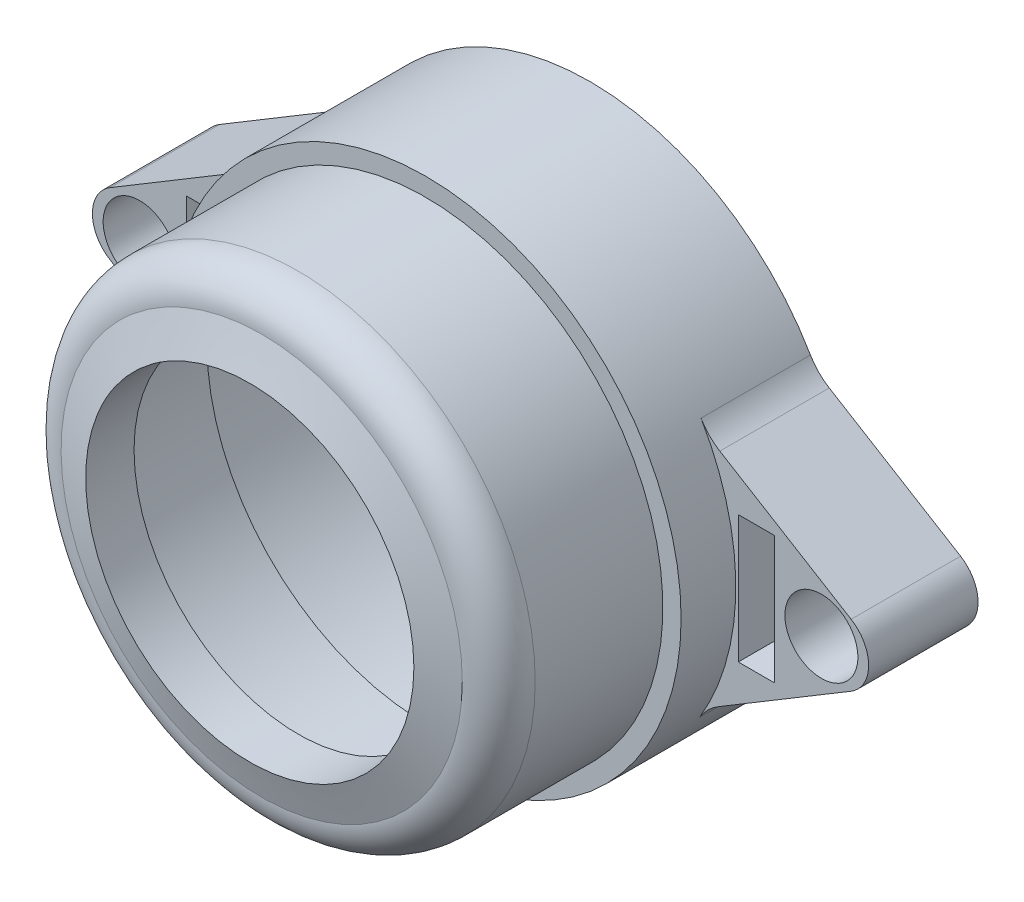
SolidWorks part; units mm, degrees
material "PE High Density"
ref_plane "Front" through (0, 0, 0) normal (0, 0, 1) x (1, 0, 0)
ref_plane "Top" through (0, 0, 0) normal (0, 1, 0) x (1, 0, 0)
ref_plane "Right" through (0, 0, 0) normal (1, 0, 0) x (0, 0, -1)
sketch "Sketch1" plane through (0, 0, 0) normal (0, 0, 1) x (1, 0, 0)
  circle A0 centre (0, 0) radius 14
extrude "Boss-Extrude1" add sketch "Sketch1" along normal blind 9 contours A0
sketch "Sketch2" plane through (0, 0, 9) normal (0, 0, 1) x (1, 0, 0)
  circle A0 centre (0, 0) radius 13
extrude "Boss-Extrude2" add sketch "Sketch2" along normal blind 9
fillet "Fillet1" radius 2 1 edges at (13, 0, 18)
sketch "Sketch3" plane through (0, 0, 18) normal (0, 0, 1) x (1, 0, 0)
  circle A0 centre (0, 0) radius 9
  circle A1 centre (0, 0) radius 8
extrude "Boss-Extrude4" add sketch "Sketch3" along normal blind 1 contours A1
loft "Loft2" add section edge at (8, 0, 19) section edge at (11, 0, 18) connector at (5.2489, -6.0373, 19) connector at (8.7002, -6.731, 18)
sketch "Sketch5" plane through (0, 0, 0) normal (0, 0, 1) x (1, 0, 0)
  line L0 (0, 14) -> (-23.147, 0.0997)
  line L1 (-23.147, 0.0997) -> (0, -14)
  line L2 (0, 14) -> (0, -14)
  circle A0 centre (0, 0) radius 14 construction
extrude "Boss-Extrude5" add sketch "Sketch5" along normal blind 6
sketch "Sketch6" plane through (0, 0, 6) normal (0, 0, 1) x (1, 0, 0)
  circle A0 centre (-18.6917, 0) radius 2
extrude "Cut-Extrude1" cut sketch "Sketch6" against normal blind 6
fillet "Fillet2" radius 2 1 edges at (-23.147, 0.0997, 3)
sketch "Sketch7" plane through (0, 0, 6) normal (0, 0, 1) x (1, 0, 0)
  line L1 (-16.134, 3.5) -> (-14.134, 3.5)
  line L2 (-16.134, 3.5) -> (-16.134, -3.5)
  line L3 (-16.134, -3.5) -> (-14.134, -3.5)
  line L4 (-14.134, 3.5) -> (-14.134, -3.5)
  line L5 (-16.134, 3.5) -> (-14.134, -3.5) construction
  line L6 (-16.134, -3.5) -> (-14.134, 3.5) construction
  point P0 (-15.134, 0)
extrude "Cut-Extrude2" cut sketch "Sketch7" against normal blind 6
sketch "Sketch9" plane through (0, 0, 0) normal (0, 0, -1) x (-1, 0, 0)
  circle A0 centre (13.1082, 4.8466) radius 1
extrude "Boss-Extrude7" add sketch "Sketch9" along normal blind 3
fillet "Fillet5" radius 1 1 edges at (-14.1082, 4.8466, -3)
fillet "Fillet6" radius 3 2 edges at (-12.44, -6.4223, 3) (-12.358, 6.5787, 3)
sketch "Sketch10" plane through (0, 0, 0) normal (0, 0, -1) x (-1, 0, 0)
  circle A0 centre (0, 0) radius 13
sketch "Sketch17" plane through (0, 0, 19) normal (0, 0, 1) x (1, 0, 0)
  circle A0 centre (0, 0) radius 9
sketch "Sketch18" plane through (-14.134, 0, 0) normal (-1, 0, 0) x (0, 0, 1)
  line L1 (-1.145, -3.5) -> (2.8192, -3.5)
  line L2 (-1.145, -3.5) -> (-1.145, 3.5)
  line L3 (-1.145, 3.5) -> (2.8192, 3.5)
  line L4 (2.8192, -3.5) -> (2.8192, 3.5)
  line L5 (-1.145, -3.5) -> (2.8192, 3.5) construction
  line L6 (-1.145, 3.5) -> (2.8192, -3.5) construction
  line L7 (0, 3.5) -> (6, 3.5) construction
extrude "Cut-Extrude3" cut sketch "Sketch18" against normal blind 3
sketch "Sketch19" plane through (-16.134, 0, 0) normal (1, 0, 0) x (0, 0, -1)
  line L1 (-1, 0.4621) -> (0, 0.4621)
  line L2 (-1, 0.4621) -> (-1, 3.5)
  line L3 (-1, 3.5) -> (0, 3.5)
  line L4 (0, 0.4621) -> (0, 3.5)
  line L5 (-1, 0.4621) -> (0, 3.5) construction
  line L6 (-1, 3.5) -> (0, 0.4621) construction
  point P0 (-0.5, 1.9811)
extrude "Boss-Extrude8" add sketch "Sketch19" along normal blind 2
pattern_circular "CirPattern2" count 2 every 180 about axis through (0, 0, 9) along (0, 0, -1) of "Boss-Extrude5", "Fillet2", "Fillet6", "Cut-Extrude1", "Boss-Extrude7", "Fillet5", "Boss-Extrude8", "Cut-Extrude2", "Cut-Extrude3" reverse direction yes
extrude "Cut-Extrude4" cut sketch "Sketch10" against normal blind 9 contours A0
sketch "Sketch20" plane through (0, 0, 9) normal (0, 0, -1) x (-1, 0, 0)
  circle A0 centre (0, 0) radius 12
extrude "Cut-Extrude6" cut sketch "Sketch20" against normal blind 7
extrude "Cut-Extrude7" cut sketch "Sketch17" against normal blind 7 contours A0
